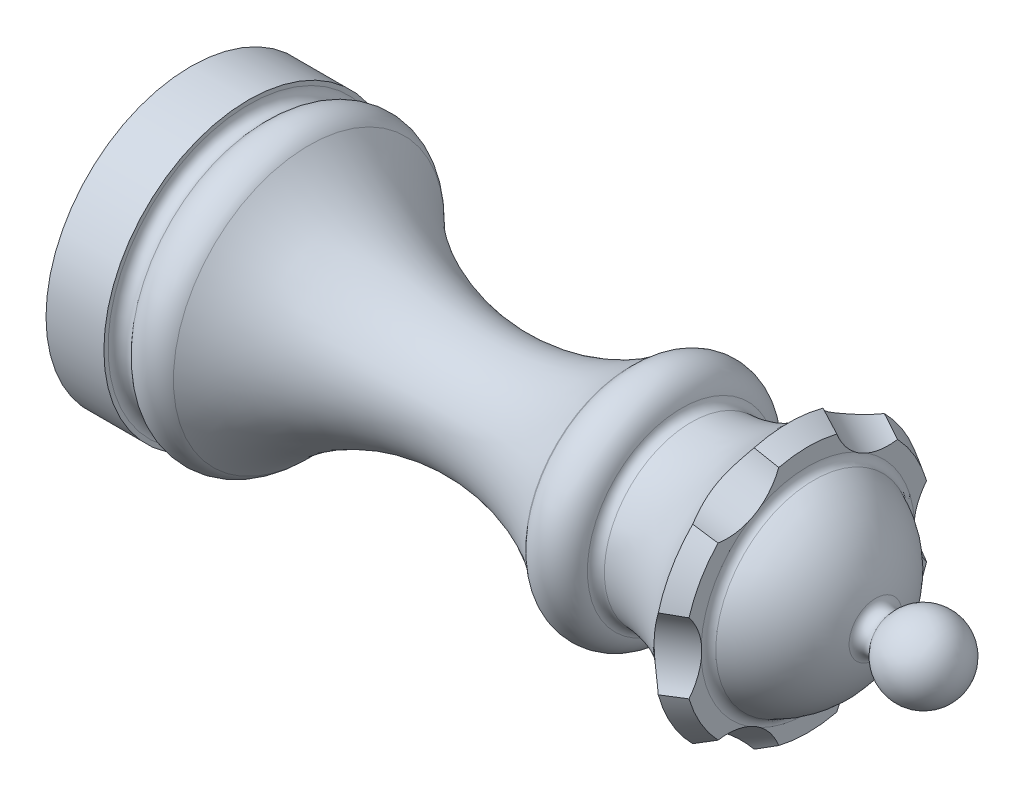
SolidWorks part; units mm, degrees
material "6061-T6 (SS)"
ref_plane "Front" through (0, 0, 0) normal (0, 0, 1) x (1, 0, 0)
ref_plane "Top" through (0, 0, 0) normal (0, 1, 0) x (1, 0, 0)
ref_plane "Right" through (0, 0, 0) normal (1, 0, 0) x (0, 0, -1)
sketch "Sketch1" plane through (0, 0, 0) normal (0, 0, 1) x (1, 0, 0)
  line L0 (0, 0) -> (0, -7.5)
  line L1 (0, -7.5) -> (3, -7.5)
  line L2 (0, 0) -> (-8.1317, 0) construction
  line L3 (0, 0) -> (40, 0)
  line L4 (3, -7.5) -> (3, -7.2856)
  line L6 (3.883, -6.9642) -> (1.6828, -4.3421) construction
  line L7 (31, -7) -> (29.2179, -4.8762) construction
  line L8 (22.8509, -5.4642) -> (17.8745, 0.4665) construction
  line L9 (24, -4.5) -> (25.5, -4.5) construction
  line L10 (32, -5.5377) -> (32, -6.4226)
  line L11 (32, -6.4226) -> (31, -7)
  arc A0 (3, -7.2856) -> (3.883, -6.9642) centre (3.5, -7.2856) cw
  arc A1 (3.883, -6.9642) -> (6.1294, -7.0227) centre (5.0321, -6) ccw
  arc A3 (22.8509, -5.4642) -> (25.4513, -4.8792) centre (24, -4.5) ccw
  arc A5 (25.958, -4.5061) -> (25.4513, -4.8792) centre (25.935, -5.0056) ccw
  arc A6 (6.1294, -7.0227) -> (22.7599, -5.3797) centre (15.3773, -15.6415) cw
  arc A7 (22.7599, -5.3797) -> (22.8509, -5.4642) centre (22.4679, -5.7856) cw
  arc A8 (40, 0) -> (36.4, -1.2) centre (38, 0) cw
  arc A9 (36.4, -1.2) -> (35.5159, -1.375) centre (36, -1.5) ccw
  arc A10 (35.5159, -1.375) -> (32.3075, -5.0762) centre (30.1905, 0) cw
  arc A11 (25.958, -4.5061) -> (31, -7) centre (25.6359, -11.501) cw
  arc A12 (32.3075, -5.0762) -> (32, -5.5377) centre (32.5, -5.5377) ccw
  arc A13 (25.958, -4.5061) -> (25.5, -4.5) centre (25.6359, -11.501) ccw construction
  arc A14 (25.4513, -4.8792) -> (25.5, -4.5) centre (24, -4.5) ccw construction
  dimension "D2" = 4
  dimension "D6" = 5.5
  dimension "D7" = 1.5
  dimension "D4" = 0.5
  dimension "D8" = 40
  dimension "D10" = 1.5
  dimension "D11" = 8
  dimension "D9" = 12
  dimension "D14" = 6
  dimension "D19" = 2
  dimension "D1" = 15
  dimension "D3" = 40
  dimension "D5" = 3
  dimension "D12" = 30
  dimension "D13" = 14
  dimension "D15" = 1
  dimension "D17" = 16
revolve "Revolve1" add sketch "Sketch1" angle 360 about L2
sketch "Sketch2" plane through (0, 0, 0) normal (0, 1, 0) x (1, 0, 0)
  line L0 (30.4354, -6.4022) -> (32, -5.4989)
  line L1 (29.5811, -10.5616) -> (29.2733, -10.7394) construction
  line L2 (32, -6.4226) -> (32, 6.4226) construction
  line L3 (31, -7) -> (32, -6.4226) construction
  line L4 (36.3371, -6.661) -> (29.2733, -10.7394)
  arc A0 (32, -5.4989) -> (36.3371, -6.661) centre (33.5875, -8.2485) cw
  arc A1 (29.2733, -10.7394) -> (30.4354, -6.4022) centre (32.0229, -9.1519) cw
  arc A2 (31, -7) -> (25.958, -4.5061) centre (25.6359, -11.501) ccw construction
  dimension "D1" = 6.35
  dimension "D2" = 0.8
revolve "Cut-Revolve1" cut sketch "Sketch2" angle 360 about L1
pattern_circular "CirPattern1" count 6 over 360 about axis through (0, 0, 0) along (1, 0, 0) of "Cut-Revolve1"
sketch "Sketch3" [suppressed] plane through (0, 0, 0) normal (1, 0, 0) x (0, 0, -1)
  line L0 (9.8288, 5.6747) -> (0, 0) construction
  line L1 (0, 0) -> (-8.6081, 4.9699) construction
  line L2 (0, 0.5774) -> (-12.7332, 7.9288)
  line L3 (0, 0.5774) -> (12.7332, 7.9288)
  line L4 (0, 10) -> (6.2765, 13.6237)
  line L5 (0, 0) -> (0, 5.4249) construction
  line L8 (0, 10) -> (-6.2765, 13.6237)
  arc A0 (12.7332, 7.9288) -> (6.2765, 13.6237) centre (0, 0) ccw
  circle A1 centre (0, 0) radius 10 construction
  arc A2 (-6.2765, 13.6237) -> (-12.7332, 7.9288) centre (0, 0) ccw
  dimension "D1" = 20
  dimension "D2" = 30
  dimension "D3" = 1
  dimension "D4" = 120
extrude "Boss-Extrude1" [suppressed] add sketch "Sketch3" along normal blind 18 from offset 2 separate body
combine bodies "Combine1" [suppressed] operation type add bodies to combine 111 108
pattern_circular "CirPattern2" [suppressed] count 3 over 360 of bodies 112
